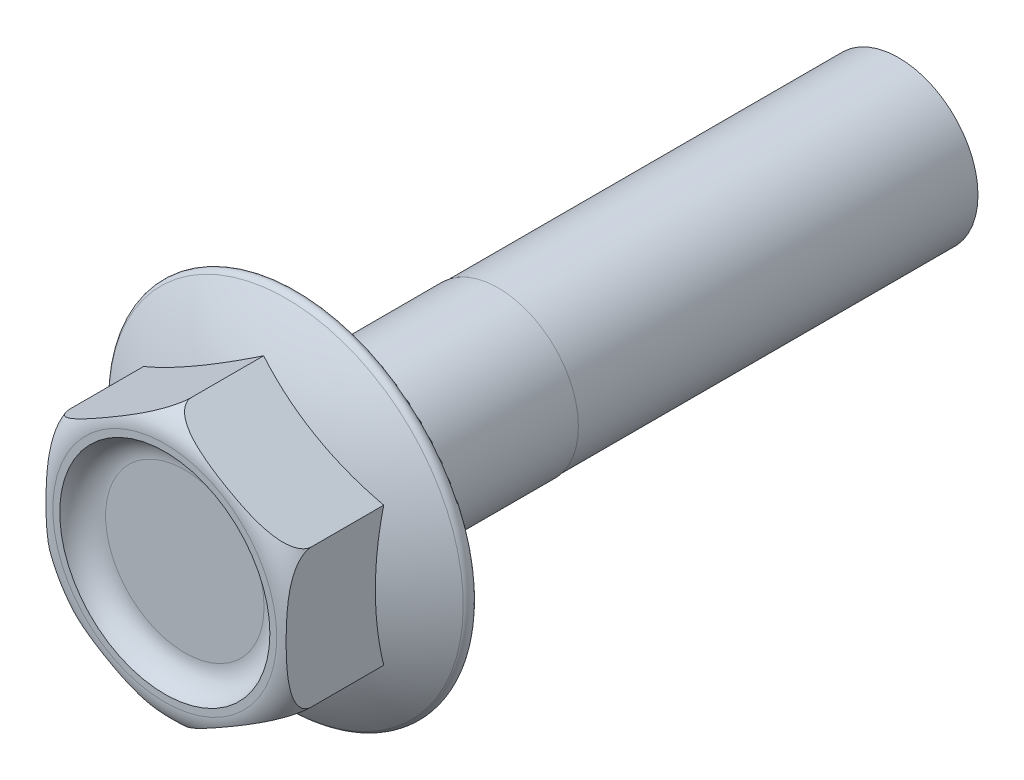
SolidWorks part; units mm, degrees
note: '?' marks a value the reader was unsure of.
extrude "Shank" add sketch "Shank Sketch" against normal blind 45
sketch "Shank Sketch" plane through (0, 0, 0) normal (0, 0, 1) x (1, 0, 0)
  line L0 (50, 0) -> (-50, 0) construction
  line L1 (0, -50) -> (0, 50) construction
  circle A0 centre (0, 0) radius 6
  dimension "Shank diameter" = 12
extrude "Head" add sketch "Head Sketch" along normal blind 10
sketch "Head Sketch" plane through (0, 0, 0) normal (0, 0, 1) x (1, 0, 0)
  line L0 (0, 10.3923) -> (9, 5.1962)
  line L1 (9, 5.1962) -> (9, -5.1962)
  line L2 (9, -5.1962) -> (0, -10.3923)
  line L3 (0, -10.3923) -> (-9, -5.1962)
  line L4 (-9, -5.1962) -> (-9, 5.1962)
  line L5 (-9, 5.1962) -> (0, 10.3923)
  line L6 (9, 5.1962) -> (-9, -5.1962) construction
  line L7 (0, 10.3923) -> (0, -10.3923) construction
  line L8 (-9, 5.1962) -> (9, -5.1962) construction
  point P0 (0, 0)
  dimension "D1" = 60
  dimension "D2" = 60
  dimension "Width across flats" = 18
ref_plane "Plane1" through (0, 0, 0) normal (0, 0, 1) x (1, 0, 0)
ref_plane "Plane2" through (0, 0, 0) normal (0, 1, 0) x (-1, 0, 0)
ref_plane "Plane3" through (0, 0, 0) normal (1, 0, 0) x (0, 0, -1)
sketch "Sketch3" plane through (0, 0, 0) normal (0, 1, 0) x (-1, 0, 0)
  line L0 (0, 0) -> (0, 10) construction
  line L1 (0, -45) -> (0, 0) construction
  line L4 (-13, 0) -> (0, 0)
  line L5 (0, 0) -> (0, 5)
  arc A0 (0, 5) -> (-13.2811, 0.9135) centre (0, -18.625) ccw
  arc A1 (-13, 0) -> (-13.2811, 0.9135) centre (-13, 0.5) cw
  dimension "D1" = 0.5
  dimension "D2" = 17
  dimension "D3" = 5
revolve "Flange" add sketch "Sketch3" angle 360 about L0
ref_axis "Axis1" through (0, 0, -95) along (0, 0, 1)?
sketch "Sketch5" plane through (0, 0, 0) normal (1, 0, 0) x (0, 0, -1)
  line L0 (-10, -8.3923) -> (-10, -10.3923)
  line L1 (-10, -10.3923) -> (-8, -10.3923)
  line L2 (-10, -10.3923) -> (-2.5915, -10.3923) construction
  line L3 (-10, -10.3923) -> (-10, -5.1962) construction
  line L5 (-15.0856, 0) -> (-8.1394, 0) construction
  line L6 (50, 0) -> (-50, 0) construction
  arc A0 (-10, -8.3923) -> (-8, -10.3923) centre (-8, -8.3923) ccw
  dimension "D1" = 2
revolve "Head Trim" cut sketch "Sketch5" angle 360 about L5
sketch "Sketch6" plane through (0, 0, 10) normal (0, 0, 1) x (1, 0, 0)
  circle A3 centre (0, 0) radius 7.875
  dimension "D1" = 11.375
extrude "Head Cut" cut sketch "Sketch6" against normal blind 1.5
fillet "Fillet1" radius 2 1 edges at (7.875, 0, 8.5)
fillet "Fillet2" radius 0.5 1 edges at (-6, 0, 0)
sketch "Thread End" plane through (0, 0, 0) normal (1, 0, 0) x (0, 0, -1)
  line L0 (15, 6) -> (15, 5.95)
  line L1 (45, 6) -> (0.5, 6) construction
  line L2 (15, 5.95) -> (45, 5.95)
  line L3 (45, 6) -> (15, 6)
  line L4 (21.5519, 0) -> (27.4271, 0) construction
  line L5 (45, 0) -> (0.5, 0) construction
  line L6 (45, -6) -> (45, 6) construction
  line L7 (45, 5.95) -> (45, 6)
  dimension "D1" = 0.05
  dimension "Length of thread" = 30
revolve "Thread Cut" cut sketch "Thread End" angle 360 about L4
cosmetic thread "Cosmetic Thread2" parameters "D2"=11
equation "\"D1@Sketch6\" = \"Width across flats@Head Sketch\"*7/8"
